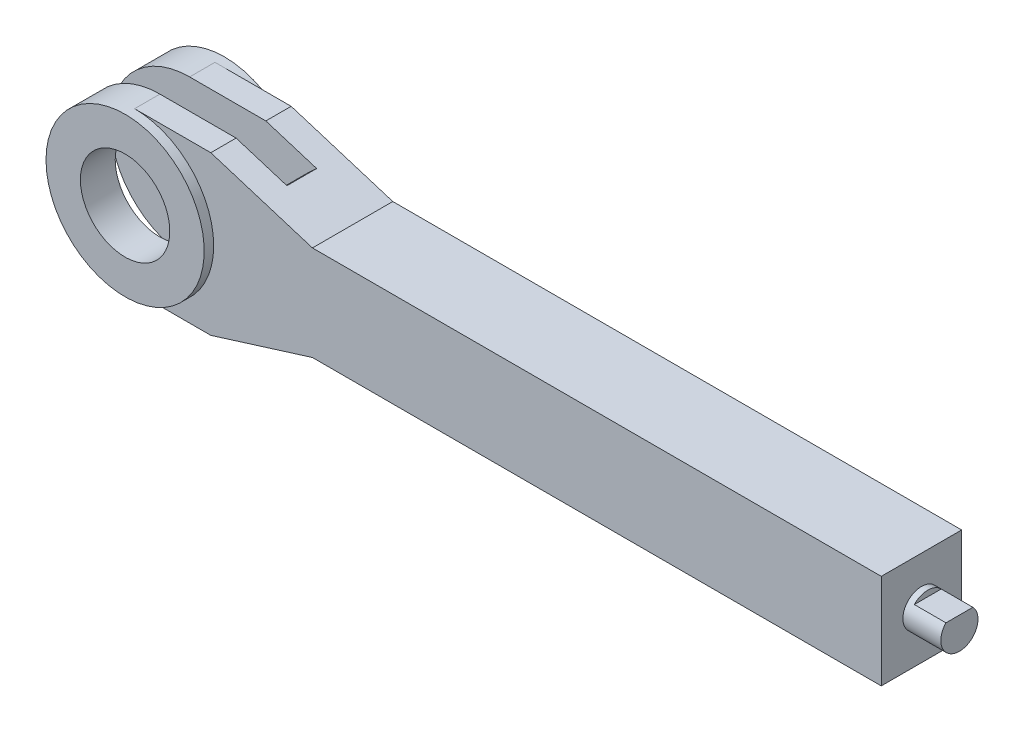
SolidWorks part; units mm, degrees
ref_plane "Front Plane" through (0, 0, 0) normal (0, 0, 1) x (1, 0, 0)
ref_plane "Top Plane" through (0, 0, 0) normal (0, 1, 0) x (1, 0, 0)
ref_plane "Right Plane" through (0, 0, 0) normal (1, 0, 0) x (0, 0, -1)
sketch "Sketch1" plane through (0, 0, 0) normal (0, 0, 1) x (1, 0, 0)
  line L0 (0, 12.5) -> (12.0413, 12.5)
  line L1 (12.0413, 12.5) -> (28.1062, 7.5)
  line L5 (28.1062, -7.5) -> (12.0413, -12.5)
  line L6 (12.0413, -12.5) -> (0, -12.5)
  line L7 (0, 0) -> (28.1062, 0) construction
  line L8 (28.1062, 7.5) -> (28.1062, -7.5)
  circle A0 centre (0, 0) radius 7.0625
  arc A1 (0, 12.5) -> (0, -12.5) centre (0, 0) ccw
  dimension "D1" = 14.125
  dimension "D2" = 25
  dimension "D3" = 15
extrude "Boss-Extrude1" add sketch "Sketch1" along normal blind 4
ref_plane "Plane1" through (0, 0, -2.35) normal (0, 0, -1) x (-1, 0, 0)
sketch "Sketch5" plane through (0, 0, 4) normal (0, 0, 1) x (1, 0, 0)
  line L0 (28.1062, 7.5) -> (28.1062, -7.5)
  line L1 (28.1062, 7.5) -> (53.6281, 7.5)
  line L3 (28.1062, -7.5) -> (53.6281, -7.5)
  line L4 (53.6281, 7.5) -> (53.6281, -7.5)
extrude "Boss-Extrude2" add sketch "Sketch5" against normal blind 12.7
mirror "Mirror1" about plane through (0, 0, -2.35) normal (0, 0, -1) of "Boss-Extrude1"
fillet "Fillet1" radius 7.5 2 edges at (28.1062, -7.5, -2.35) (28.1062, 7.5, -2.35)
sketch "Sketch6" plane through (0, 0, -2.35) normal (0, 0, -1) x (-1, 0, 0)
  line L0 (-28.1062, -7.5) -> (-53.6281, -7.5) construction
  line L1 (-53.6281, 7.5) -> (-118, 7.5)
  line L2 (-53.6281, 7.5) -> (-53.6281, -7.5)
  line L3 (-53.6281, -7.5) -> (-118, -7.5)
  line L4 (-118, 7.5) -> (-118, -7.5)
  point P8 (-118, 0)
  dimension "D1" = 118
extrude "Boss-Extrude3" add sketch "Sketch6" along normal mid plane 4
chamfer "Chamfer1" distance 10 distance2 6 2 edges at (53.6281, 7.5, 1.825) (53.6281, 7.5, -6.525) first distance on face at (52.8458, 7.5, -2.35)
chamfer "Chamfer2" distance 6 distance2 10 2 edges at (53.6281, -7.5, 1.825) (53.6281, -7.5, -6.525) first distance on face at (53.6281, -3, 1.825) first distance on face at (53.6281, -3, -6.525)
sketch "Sketch8" plane through (118, 0, 0) normal (1, 0, 0) x (0, 0, -1)
  line L0 (2.35, -16.9531) -> (2.35, 16.9531) construction
  circle A0 centre (2.35, 0) radius 2.9375
  dimension "D1" = 5.875
extrude "Boss-Extrude4" add sketch "Sketch8" along normal blind 6
sketch "Sketch9" plane through (0, 0, 0) normal (0, 1, 0) x (1, 0, 0)
  line L0 (53.6281, 8.7) -> (53.6281, 4.35) construction
  line L1 (53.6281, 6.525) -> (98.3499, 6.525)
  line L2 (53.6281, 6.525) -> (53.6281, -1.825)
  line L3 (53.6281, -1.825) -> (98.3499, -1.825)
  line L5 (92.9263, 2.35) -> (50092.9263, 2.35) construction
  line L6 (16.9531, 2.35) -> (-16.9531, 2.35) construction
  line L7 (98.3499, 6.525) -> (112.8561, 2.35)
  line L8 (112.8561, 2.35) -> (98.3499, -1.825)
extrude "Boss-Extrude5" add sketch "Sketch9" along normal mid plane 3
sketch "Sketch11" plane through (118, 0, 0) normal (-1, 0, 0) x (0, 0, 1)
  line L5 (-5.7213, -4.3444) -> (1.0213, -4.3444)
  line L6 (-5.7213, -4.3444) -> (-5.7213, 4.3444)
  line L7 (-5.7213, 4.3444) -> (1.0213, 4.3444)
  line L8 (1.0213, -4.3444) -> (1.0213, 4.3444)
extrude "Boss-Extrude7" add sketch "Sketch11" along normal blind 8
fillet "Fillet2" radius 2.5 4 edges at (114, 4.3444, 1.0213) (114, -4.3444, 1.0213) (114, 4.3444, -5.7213) (114, -4.3444, -5.7213)
sketch "Sketch12" plane through (0, 0, -8.7) normal (0, 0, -1) x (-1, 0, 0)
  circle A0 centre (0, 0) radius 7.0625 construction
  circle A1 centre (0, 0) radius 7.0625
  circle A2 centre (0, 0) radius 12.5
extrude "Boss-Extrude8" add sketch "Sketch12" along normal blind 1.5
mirror "Mirror2" about plane through (0, 0, -2.35) normal (0, 0, -1) of "Boss-Extrude8"
sketch "Sketch13" plane through (124, 0, 0) normal (1, 0, 0) x (0, 0, -1)
  line L0 (4.4765, 2.0266) -> (0.2235, 2.0266)
  circle A1 centre (2.35, 0) radius 2.9375
  arc A2 (4.4765, 2.0266) -> (0.2235, 2.0266) centre (2.35, 0) ccw
  dimension "D1" = 0
extrude "Cut-Extrude2" cut sketch "Sketch13" against normal blind 5
sketch "Sketch14" plane through (0, 0, -0.35) normal (0, 0, 1) x (1, 0, 0)
  line L0 (118, 4.3444) -> (118, -4.3444)
  line L1 (53.6281, 1.5) -> (53.6281, -1.5)
  line L12 (110, -4.3444) -> (110, 4.3444)
  line L13 (110, 4.3444) -> (118, 4.3444)
  line L14 (118, 4.3444) -> (118, 7.5)
  line L15 (118, 7.5) -> (43.6281, 7.5)
  line L16 (43.6281, 7.5) -> (53.6281, 1.5)
  line L17 (53.6281, 1.5) -> (105.907, 1.5)
  line L18 (105.907, 1.5) -> (105.907, -1.5)
  line L19 (105.907, -1.5) -> (53.6281, -1.5)
  line L20 (53.6281, -1.5) -> (43.6281, -7.5)
  line L21 (43.6281, -7.5) -> (118, -7.5)
  line L22 (118, -7.5) -> (118, -4.3444)
  line L23 (118, -4.3444) -> (110, -4.3444)
  line L26 (118, 4.3444) -> (118, 7.5)
  line L27 (118, 7.5) -> (43.6281, 7.5)
  line L28 (43.6281, 7.5) -> (53.6281, 1.5)
  line L32 (53.6281, -1.5) -> (43.6281, -7.5)
  line L33 (43.6281, -7.5) -> (118, -7.5)
  line L34 (118, -7.5) -> (118, -4.3444)
  dimension "D1" = 0
extrude "Boss-Extrude10" add sketch "Sketch14" along normal up to surface (4.35 mm away) up to face at (28.7307, 0, 4)
sketch "Sketch15" plane through (0, 0, -4.35) normal (0, 0, -1) x (-1, 0, 0)
  line L0 (-118, 4.3444) -> (-118, -4.3444)
  line L1 (-43.6281, 7.5) -> (-43.6281, -7.5)
  line L12 (-118, 4.3444) -> (-110, 4.3444)
  line L13 (-110, 4.3444) -> (-110, -4.3444)
  line L14 (-110, -4.3444) -> (-118, -4.3444)
  line L15 (-118, -4.3444) -> (-118, -7.5)
  line L16 (-118, -7.5) -> (-43.6281, -7.5)
  line L17 (-43.6281, -7.5) -> (-53.6281, -1.5)
  line L18 (-53.6281, -1.5) -> (-105.907, -1.5)
  line L19 (-105.907, -1.5) -> (-105.907, 1.5)
  line L20 (-105.907, 1.5) -> (-53.6281, 1.5)
  line L21 (-53.6281, 1.5) -> (-43.6281, 7.5)
  line L22 (-43.6281, 7.5) -> (-118, 7.5)
  line L23 (-118, 7.5) -> (-118, 4.3444)
  line L27 (-118, -4.3444) -> (-118, -7.5)
  line L28 (-118, -7.5) -> (-43.6281, -7.5)
  line L29 (-43.6281, -7.5) -> (-53.6281, -1.5)
  line L34 (-43.6281, 7.5) -> (-118, 7.5)
  line L35 (-118, 7.5) -> (-118, 4.3444)
  dimension "D1" = 0
extrude "Boss-Extrude11" add sketch "Sketch15" along normal up to surface (4.35 mm away) contours L1 L34 L35 L0 L27 L28 up to face at (28.7307, 0, -8.7)
sketch "Sketch16" plane through (0, 0, 0) normal (0, 0, -1) x (-1, 0, 0)
  line L6 (0, 12.5) -> (-12.0413, 12.5)
  line L7 (-12.0413, 12.5) -> (-28.1062, 7.5)
  line L8 (-28.1062, 7.5) -> (-35.6062, 7.5)
  line L9 (-35.6062, -7.5) -> (-28.1062, -7.5)
  line L10 (-28.1062, -7.5) -> (-12.0413, -12.5)
  line L11 (-12.0413, -12.5) -> (0, -12.5)
  line L13 (-20.0738, 10) -> (-28.1062, 7.5)
  line L14 (-28.1062, 7.5) -> (-35.6062, 7.5)
  line L15 (-35.6062, -7.5) -> (-28.1062, -7.5)
  line L16 (-28.1062, -7.5) -> (-20.0738, -10)
  arc A0 (-20.0738, -10) -> (-20.0738, 10) centre (-28.1062, 0) ccw
  arc A3 (0, -12.5) -> (0, 12.5) centre (0, 0) ccw
  arc A4 (-28.1062, 0) -> (-35.6062, 7.5) centre (-35.6062, 0) ccw
  arc A5 (-35.6062, -7.5) -> (-28.1062, 0) centre (-35.6062, 0) ccw
  arc A7 (-28.1062, 0) -> (-35.6062, 7.5) centre (-35.6062, 0) ccw
  arc A8 (-35.6062, -7.5) -> (-28.1062, 0) centre (-35.6062, 0) ccw
  dimension "D1" = 0
extrude "Boss-Extrude12" add sketch "Sketch16" along normal up to surface (8.7 mm away) up to face at (41.0994, 0, -8.7)
